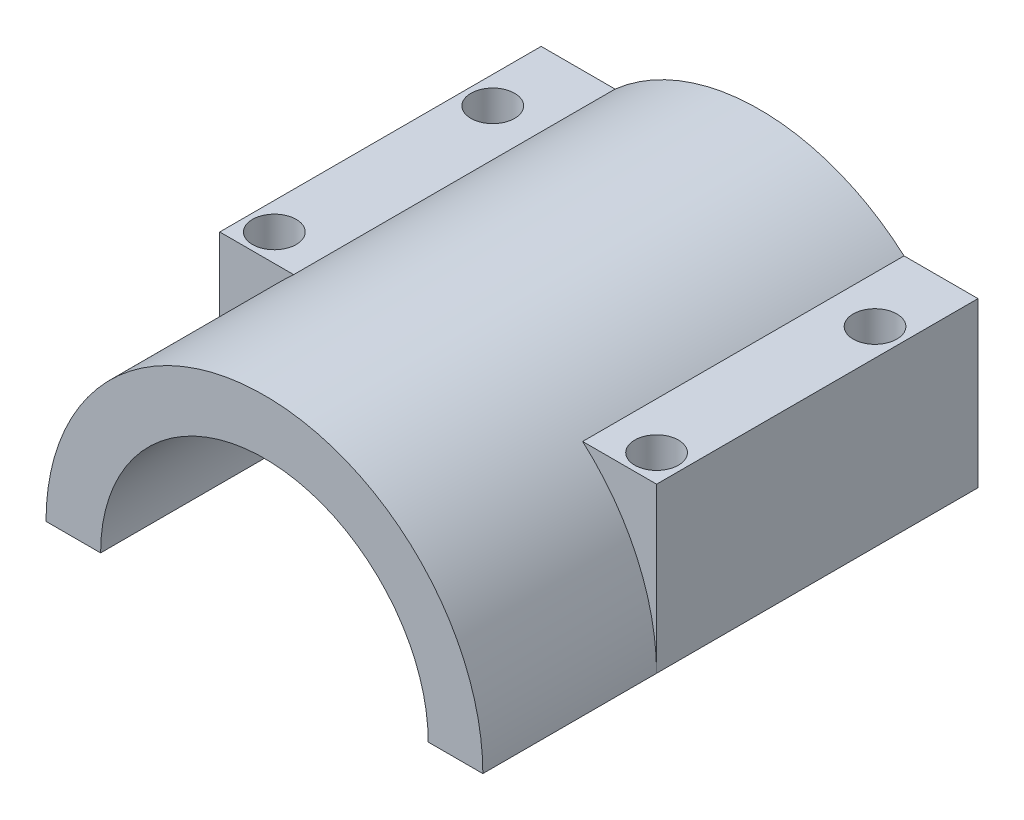
SolidWorks part; units mm, degrees
ref_plane "Front Plane" through (0, 0, 0) normal (0, 0, 1) x (1, 0, 0)
ref_plane "Top Plane" through (0, 0, 0) normal (0, 1, 0) x (1, 0, 0)
ref_plane "Right Plane" through (0, 0, 0) normal (1, 0, 0) x (0, 0, -1)
sketch "Sketch1" plane through (0, 0, 0) normal (0, 0, 1) x (1, 0, 0)
  line L0 (0, -55) -> (0, 55) construction
  line L1 (55, 0) -> (-55, 0) construction
  circle A0 centre (0, 0) radius 18.415 construction
  circle A1 centre (0, 7) radius 6 construction
  dimension "D1" = 12
  dimension "D3" = 36.83
  dimension "D2" = 7
sketch "Sketch2" plane through (0, 0, 0) normal (0, 0, 1) x (1, 0, 0)
  line L0 (-19.05, 0) -> (-25.4, 0)
  line L1 (20.2565, 0) -> (-20.2565, 0) construction
  line L2 (19.05, 0) -> (25.4, 0)
  arc A1 (19.05, 0) -> (-19.05, 0) centre (0, 0) ccw
  arc A2 (-25.4, 0) -> (25.4, 0) centre (0, 0) cw
  dimension "D1" = 38.1
  dimension "D2" = 6.35
extrude "Boss-Extrude1" add sketch "Sketch2" along normal blind 52.578
sketch "Sketch3" plane through (0, 0, 0) normal (0, 0, -1) x (-1, 0, 0)
  line L0 (-25.4, 0) -> (25.4, 0)
  circle A0 centre (0, 7) radius 6 construction
  circle A1 centre (0, 7) radius 6
  arc A2 (25.4, 0) -> (-25.4, 0) centre (0, 0) ccw construction
  arc A3 (25.4, 0) -> (-25.4, 0) centre (0, 0) ccw
extrude "Boss-Extrude2" add sketch "Sketch3" along normal blind 5
sketch "Sketch4" plane through (0, 0, 0) normal (0, 1, 0) x (1, 0, 0)
  line L0 (0, -24.0983) -> (0, 24.0983) construction
  line L1 (-22.225, -29.2) -> (22.225, -29.2) construction
  line L2 (-22.225, -29.2) -> (-22.225, -3.8) construction
  line L3 (-22.225, -3.8) -> (22.225, -3.8) construction
  line L4 (22.225, -29.2) -> (22.225, -3.8) construction
  line L5 (-22.225, -29.2) -> (22.225, -3.8) construction
  line L6 (-22.225, -3.8) -> (22.225, -29.2) construction
  line L7 (25.4, 5) -> (-25.4, 5) construction
  circle A0 centre (-22.225, -3.8) radius 2.54
  circle A1 centre (22.225, -3.8) radius 2.54
  circle A2 centre (22.225, -29.2) radius 2.54
  circle A3 centre (-22.225, -29.2) radius 2.54
  point P0 (0, -16.5)
  dimension "D2" = 5.08
  dimension "D3" = 25.4
  dimension "D1" = 8.8
  dimension "D4" = 44.45
extrude "Cut-Extrude1" cut sketch "Sketch4" along normal through all
sketch "Sketch5" plane through (0, 0, 0) normal (0, -1, 0) x (1, 0, 0)
  line L0 (-25.4, 52.578) -> (-25.4, -5) construction
  circle A0 centre (-22.225, 29.2) radius 2.54
  circle A1 centre (-22.225, 29.2) radius 3.175
  circle A2 centre (-22.225, 29.2) radius 2.54 construction
  circle A3 centre (-22.225, 3.8) radius 2.54
  circle A4 centre (-22.225, 3.8) radius 3.175
  circle A5 centre (22.225, 3.8) radius 2.54
  circle A6 centre (22.225, 3.8) radius 3.175
  circle A7 centre (22.225, 29.2) radius 2.54
  circle A8 centre (22.225, 29.2) radius 3.175
extrude "Boss-Extrude3" add sketch "Sketch5" against normal blind 19.05
sketch "Sketch6" plane through (0, 19.05, 0) normal (0, 1, 0) x (1, 0, 0)
  line L1 (-16.51, -32.375) -> (-25.4, -32.375)
  line L2 (-16.51, -32.375) -> (-16.51, 5)
  line L3 (-16.51, 5) -> (-25.4, 5)
  line L4 (-25.4, -32.375) -> (-25.4, 5)
  line L5 (-16.51, -32.375) -> (-25.4, 5) construction
  line L6 (-16.51, 5) -> (-25.4, -32.375) construction
  circle A0 centre (-22.225, -29.2) radius 3.175 construction
  circle A1 centre (-22.225, -29.2) radius 2.54
  circle A2 centre (-22.225, -29.2) radius 2.54 construction
  circle A3 centre (-22.225, -3.8) radius 2.54
  circle A4 centre (-22.225, -3.8) radius 2.54 construction
  point P4 (-20.955, -13.6875)
  dimension "D1" = 8.89
extrude "Boss-Extrude4" add sketch "Sketch6" against normal up to surface (19.05 mm away) up to face at (0, 9.7986, 18.9297)
mirror "Mirror1" about plane through (0, 0, 0) normal (1, 0, 0) of "Boss-Extrude4"
